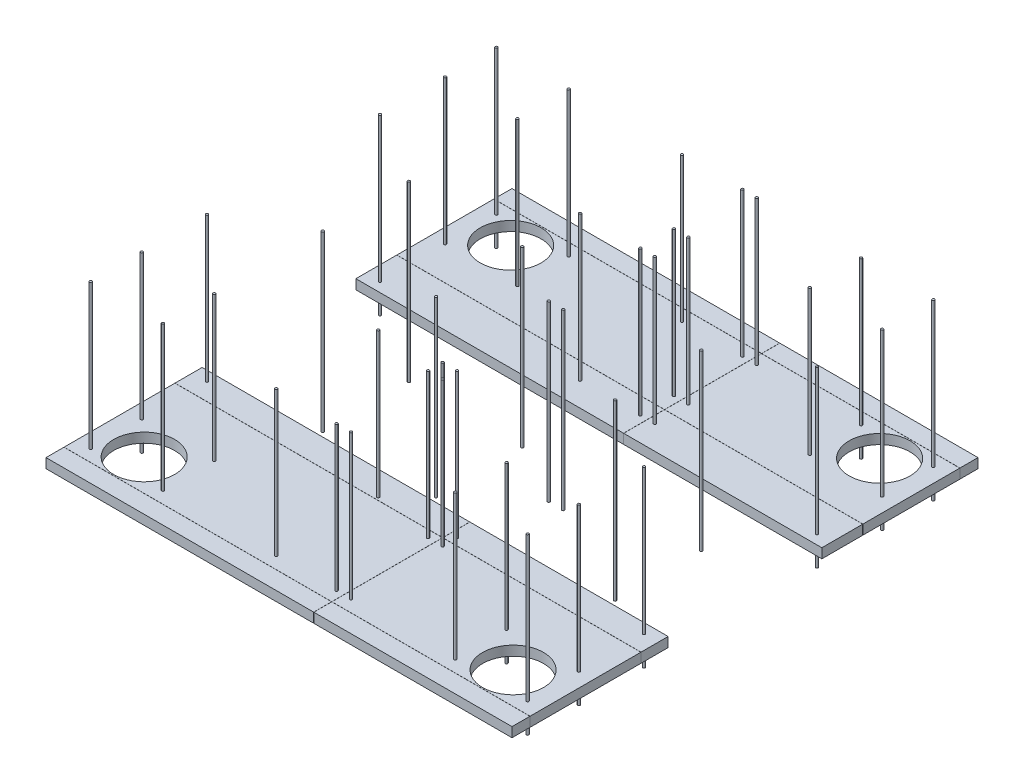
SolidWorks part; units mm, degrees
ref_plane "Front" through (0, 0, 0) normal (0, 0, 1) x (1, 0, 0)
ref_plane "Top" through (0, 0, 0) normal (0, 1, 0) x (1, 0, 0)
ref_plane "Right" through (0, 0, 0) normal (1, 0, 0) x (0, 0, -1)
sketch "Sketch1" plane through (0, 0, 0) normal (0, 1, 0) x (1, 0, 0)
  line L1 (-2454.275, 2454.275) -> (2454.275, 2454.275)
  line L2 (-2454.275, 2454.275) -> (-2454.275, -2454.275)
  line L3 (-2454.275, -2454.275) -> (2454.275, -2454.275)
  line L4 (2454.275, 2454.275) -> (2454.275, -2454.275)
  line L5 (-2454.275, 2454.275) -> (2454.275, -2454.275) construction
  line L6 (-2454.275, -2454.275) -> (2454.275, 2454.275) construction
  point P0 (0, 0)
  dimension "D1" = 4908.55
  dimension "D2" = 4908.55
extrude "Boss-Extrude1" add sketch "Sketch1" along normal blind 101.6
sketch "Sketch2" plane through (0, 101.6, 0) normal (0, 1, 0) x (1, 0, 0)
  line L0 (-2454.275, 2454.275) -> (-2454.275, -2454.275) construction
  line L1 (2454.275, -809.625) -> (-2454.275, -809.625)
  line L2 (2454.275, -809.625) -> (2454.275, 809.625)
  line L3 (2454.275, 809.625) -> (-2454.275, 809.625)
  line L4 (-2454.275, -809.625) -> (-2454.275, 809.625)
  line L5 (2454.275, -809.625) -> (-2454.275, 809.625) construction
  line L6 (2454.275, 809.625) -> (-2454.275, -809.625) construction
  point P0 (0, 0)
  dimension "D1" = 1619.25
extrude "Cut-Extrude1" cut sketch "Sketch2" against normal through all
sketch "Sketch4" plane through (0, 101.6, 0) normal (0, 1, 0) x (1, 0, 0)
  line L0 (-2454.275, -2263.775) -> (2454.275, -2263.775)
  line L3 (-2454.275, -2454.275) -> (2454.275, -2454.275) construction
  line L4 (-2454.275, -1095.375) -> (2454.275, -1095.375)
  line L5 (-2454.275, -809.625) -> (-2454.275, -2454.275) construction
  line L6 (-2454.275, -809.625) -> (2454.275, -809.625) construction
  line L7 (-2454.275, 2263.775) -> (2454.275, 2263.775)
  line L10 (-2454.275, 1241.425) -> (2454.275, 1241.425)
  line L11 (-2454.275, 2454.275) -> (-2454.275, 809.625) construction
  line L12 (2454.275, 809.625) -> (2454.275, 2454.275) construction
  line L13 (2454.275, 2454.275) -> (-2454.275, 2454.275) construction
  line L14 (2454.275, 809.625) -> (-2454.275, 809.625) construction
  line L15 (-2454.275, -1095.375) -> (-2454.275, -2263.775) construction
  line L16 (2454.275, -1095.375) -> (2454.275, -2263.775) construction
  line L17 (2454.275, 1241.425) -> (2454.275, 2263.775) construction
  line L18 (-2454.275, 1241.425) -> (-2454.275, 2263.775) construction
  line L19 (2454.275, -2454.275) -> (2454.275, -809.625) construction
  dimension "D1" = 190.5
  dimension "D2" = 1168.4
  dimension "D3" = 285.75
  dimension "D4" = 190.5
  dimension "D5" = 1022.35
  dimension "D6" = 431.8
extrude "Cut-Extrude-Thin1" cut sketch "Sketch4" against normal through all thin thin type one direction wall 1.27
sketch "Sketch5" plane through (0, 101.6, 0) normal (0, 1, 0) x (1, 0, 0)
  line L0 (365.125, -2454.275) -> (365.125, 2454.275)
  line L1 (-2454.275, -2454.275) -> (2454.275, -2454.275) construction
  line L2 (2454.275, 2454.275) -> (-2454.275, 2454.275) construction
  line L3 (2454.275, -2263.775) -> (2454.275, -1096.645) construction
  line L4 (-2454.275, -1096.645) -> (-2454.275, -2263.775) construction
  dimension "D1" = 2089.15
  dimension "D2" = 2819.4
extrude "Cut-Extrude-Thin2" cut sketch "Sketch5" against normal through all and the other way through all thin thin type one direction wall 1.27
sketch "Sketch8" plane through (0, 101.6, 0) normal (0, 1, 0) x (1, 0, 0)
  line L0 (-974.0807, 502.3386) -> (-974.0807, 1597.0052) construction
sketch "Sketch6" plane through (0, 101.6, 0) normal (0, 1, 0) x (1, 0, 0)
  line L0 (1943.1, 1929.13) -> (1943.1, 2262.505) construction
  line L1 (-1943.1, 1929.13) -> (1943.1, 1929.13) construction
  line L2 (-1943.1, 1929.13) -> (-1943.1, -1931.67) construction
  line L3 (-1943.1, -1931.67) -> (1943.1, -1931.67) construction
  line L4 (1943.1, 1929.13) -> (1943.1, -1931.67) construction
  line L5 (-1943.1, -1931.67) -> (-1943.1, -2265.045) construction
  line L6 (-2454.275, -2265.045) -> (365.125, -2265.045) construction
  line L7 (366.395, 2262.505) -> (2454.275, 2262.505) construction
  line L9 (2454.275, 1241.425) -> (2454.275, 2262.505) construction
  line L11 (-2454.275, -1096.645) -> (-2454.275, -2263.775) construction
  circle A0 centre (1943.1, 1929.13) radius 320.675
  circle A1 centre (-1943.1, 1929.13) radius 320.675
  circle A2 centre (-1943.1, -1931.67) radius 320.675
  circle A3 centre (1943.1, -1931.67) radius 320.675
  dimension "D1" = 641.35
  dimension "D3" = 190.5
  dimension "D4" = 190.5
  dimension "D2" = 12.7
extrude "DUCT HOLES" cut sketch "Sketch6" against normal through all
sketch "Sketch7" plane through (0, 101.6, 0) normal (0, 1, 0) x (1, 0, 0)
  line L0 (-1539.875, 2301.875) -> (-346.075, 2301.875) construction
  line L1 (-1539.875, 2301.875) -> (-2454.275, 2301.875) construction
  line L2 (-2454.275, 2454.275) -> (-2454.275, 2263.775) construction
  line L3 (365.125, 2454.275) -> (-2454.275, 2454.275) construction
  line L4 (-346.075, 2301.875) -> (365.125, 2301.875) construction
  line L5 (365.125, 2263.775) -> (365.125, 2454.275) construction
  line L6 (1539.875, 1597.025) -> (1539.875, 1063.625) construction
  line L7 (365.125, 2301.875) -> (974.725, 2301.875) construction
  line L8 (974.725, 2301.875) -> (1539.875, 2301.875) construction
  line L9 (1539.875, 2301.875) -> (2454.275, 2301.875) construction
  line L10 (2454.275, 2263.775) -> (2454.275, 2454.275) construction
  line L11 (366.395, 2263.775) -> (366.395, 2454.275) construction
  line L12 (2454.275, 1597.025) -> (-2454.275, 1597.025) construction
  line L13 (2454.275, 1241.425) -> (2454.275, 2262.505) construction
  line L14 (-2454.275, 2262.505) -> (-2454.275, 1241.425) construction
  line L15 (1539.875, 2301.875) -> (1539.875, 1597.025) construction
  line L16 (-2454.275, 1241.425) -> (365.125, 1241.425) construction
  line L17 (-346.075, 2301.875) -> (-346.075, 1597.025) construction
  line L18 (974.725, 2301.875) -> (974.725, 1597.025) construction
  line L19 (-2454.275, 2136.775) -> (2454.275, 2136.775) construction
  line L20 (-2454.275, 2263.775) -> (365.125, 2263.775) construction
  line L21 (-1539.875, 2301.875) -> (-1539.875, 2136.775) construction
  line L22 (-2454.275, 1063.625) -> (2454.275, 1063.625) construction
  line L23 (-2454.275, 1240.155) -> (-2454.275, 809.625) construction
  line L24 (2454.275, 809.625) -> (2454.275, 1240.155) construction
  line L25 (365.125, 809.625) -> (-2454.275, 809.625) construction
  line L26 (-1539.875, 1063.625) -> (-1539.875, 1597.025) construction
  line L27 (-346.075, 1597.025) -> (-346.075, 1063.625) construction
  line L28 (-2107.4102, -2022.1425) -> (-2107.4102, -819.4758) construction
  line L29 (-1539.875, 1285.875) -> (1539.875, 1285.875) construction
  line L30 (-2301.875, 1597.025) -> (-2301.875, 1063.625) construction
  line L31 (2301.875, 1597.025) -> (2301.875, 1063.625) construction
  line L32 (-2454.275, 1240.155) -> (365.125, 1240.155) construction
  line L33 (441.325, 1063.625) -> (288.925, 1063.625) construction
  line L34 (441.325, 1063.625) -> (441.325, 1416.685) construction
  line L35 (441.325, 1416.685) -> (288.925, 1416.685) construction
  line L36 (288.925, 1063.625) -> (288.925, 1416.685) construction
  line L37 (-2454.275, 1240.155) -> (365.125, 1240.155) construction
  line L38 (365.125, 809.625) -> (365.125, 1240.155) construction
  line L39 (365.125, 809.625) -> (365.125, 1240.155) construction
  line L40 (440.6472, 1241.425) -> (440.6472, 1063.625) construction
  line L41 (288.925, -1172.845) -> (441.325, -1172.845) construction
  line L42 (288.925, -1172.845) -> (288.925, -1020.445) construction
  line L43 (288.925, -1020.445) -> (441.325, -1020.445) construction
  line L44 (441.325, -1172.845) -> (441.325, -1020.445) construction
  line L45 (366.395, 1241.425) -> (2454.275, 1241.425) construction
  line L46 (1539.875, 1063.625) -> (1539.875, -2454.275) construction
  line L47 (366.395, -2454.275) -> (2454.275, -2454.275) construction
  line L48 (-2454.275, -1096.645) -> (365.125, -1096.645) construction
  line L49 (-2454.275, -1096.645) -> (365.125, -1096.645) construction
  line L50 (-2301.875, 1063.625) -> (-2301.875, 911.225) construction
  line L51 (-2301.875, 911.225) -> (2301.875, 911.225) construction
  line L52 (2301.875, 911.225) -> (2301.875, 1063.625) construction
  line L53 (-1539.875, 1063.625) -> (-1539.875, -2454.275) construction
  line L54 (-2454.275, -2454.275) -> (365.125, -2454.275) construction
  line L55 (1539.875, 454.025) -> (-1539.875, 454.025) construction
  line L56 (288.925, 1063.625) -> (288.925, -2454.275) construction
  line L57 (441.325, 1063.625) -> (441.325, -2454.275) construction
  line L58 (-346.075, 1063.625) -> (-346.075, -2454.275) construction
  line L59 (441.325, 98.425) -> (288.925, 98.425) construction
  line L60 (441.325, 1063.625) -> (441.325, 2301.875) construction
  line L61 (288.925, 1063.625) -> (288.925, 2301.875) construction
  circle A0 centre (-1539.875, 2301.875) radius 12.7 construction
  circle A4 centre (1539.875, 1597.025) radius 12.7
  circle A5 centre (-1539.875, 1597.025) radius 12.7
  circle A6 centre (441.325, 1063.625) radius 12.7
  circle A7 centre (-346.075, 1597.025) radius 12.7 construction
  circle A8 centre (974.725, 1597.025) radius 12.7 construction
  circle A9 centre (-346.075, 2136.775) radius 12.7
  circle A10 centre (-1539.875, 2136.775) radius 12.7
  circle A11 centre (974.725, 2136.775) radius 12.7 construction
  circle A12 centre (1539.875, 2136.775) radius 12.7
  circle A13 centre (-346.075, 1063.625) radius 12.7
  circle A14 centre (-1539.875, 1063.625) radius 12.7 construction
  circle A15 centre (1539.875, 1063.625) radius 12.7 construction
  circle A16 centre (-2301.875, 1597.025) radius 12.7
  circle A17 centre (2301.875, 1597.025) radius 12.7
  circle A18 centre (-2301.875, 2136.775) radius 12.7
  circle A19 centre (2301.875, 2136.775) radius 12.7
  circle A20 centre (219.075, 2301.875) radius 12.7 construction
  circle A21 centre (658.495, 2301.875) radius 12.7 construction
  circle A22 centre (1539.875, 2301.875) radius 12.7 construction
  circle A23 centre (-650.875, 2301.875) radius 12.7 construction
  circle A24 centre (-1539.875, 1285.875) radius 12.7 construction
  circle A25 centre (1539.875, 1285.875) radius 12.7 construction
  circle A26 centre (-2301.875, 1063.625) radius 12.7 construction
  circle A27 centre (2301.875, 1063.625) radius 12.7 construction
  circle A28 centre (288.925, 1416.685) radius 12.7
  circle A29 centre (441.325, 1416.685) radius 12.7
  circle A30 centre (288.925, 1063.625) radius 12.7
  circle A31 centre (441.325, -1020.445) radius 12.7
  circle A32 centre (288.925, -1020.445) radius 12.7
  circle A33 centre (288.925, -1172.845) radius 12.7
  circle A34 centre (441.325, -1172.845) radius 12.7
  circle A35 centre (-2301.875, 911.225) radius 12.7
  circle A36 centre (2301.875, 911.225) radius 12.7
  circle A37 centre (1539.875, 454.025) radius 12.7
  circle A38 centre (-1539.875, 454.025) radius 12.7
  circle A41 centre (-346.075, 454.025) radius 12.7
  circle A43 centre (441.325, 98.425) radius 12.7
  circle A44 centre (288.925, 98.425) radius 12.7
  circle A45 centre (288.925, 2136.775) radius 12.7
  circle A47 centre (441.325, 2136.775) radius 12.7
  point P107 (288.925, -1096.645)
  dimension "D1" = 25.4
  dimension "D5" = 609.6
  dimension "D7" = 355.6
  dimension "D11" = 152.4
  dimension "D14" = 152.4
  dimension "D19" = 889
  dimension "D20" = 914.4
  dimension "D21" = 1168.4
  dimension "D25" = 457.2
  dimension "D26" = 355.6
  dimension "D2" = 152.4
  dimension "D3" = 914.4
  dimension "D4" = 711.2
  dimension "D6" = 914.4
  dimension "D8" = 914.4
  dimension "D9" = 127
  dimension "D10" = 152.4
  dimension "D12" = 254
  dimension "D13" = 152.4
  dimension "D15" = 152.4
  dimension "D16" = 146.05
  dimension "D17" = 292.1
  dimension "D18" = 914.4
  dimension "D22" = 3079.75
  dimension "D23" = 152.4
  dimension "D24" = 152.4
extrude "UNISTRUT STUD LAYOUT" add sketch "Sketch7" along normal blind 1524 and the other way blind 304.8 separate body
mirror "Mirror3" about plane through (0, 0, 0) normal (0, 0, 1) of bodies 251 238 222 252 271 272 286 302 301 306 309 305 316 315 317 320 321 240 223 227 214 225 241 215 226 224 228 217 244 229 216 275 276 277 281 283 287 288 293 291
